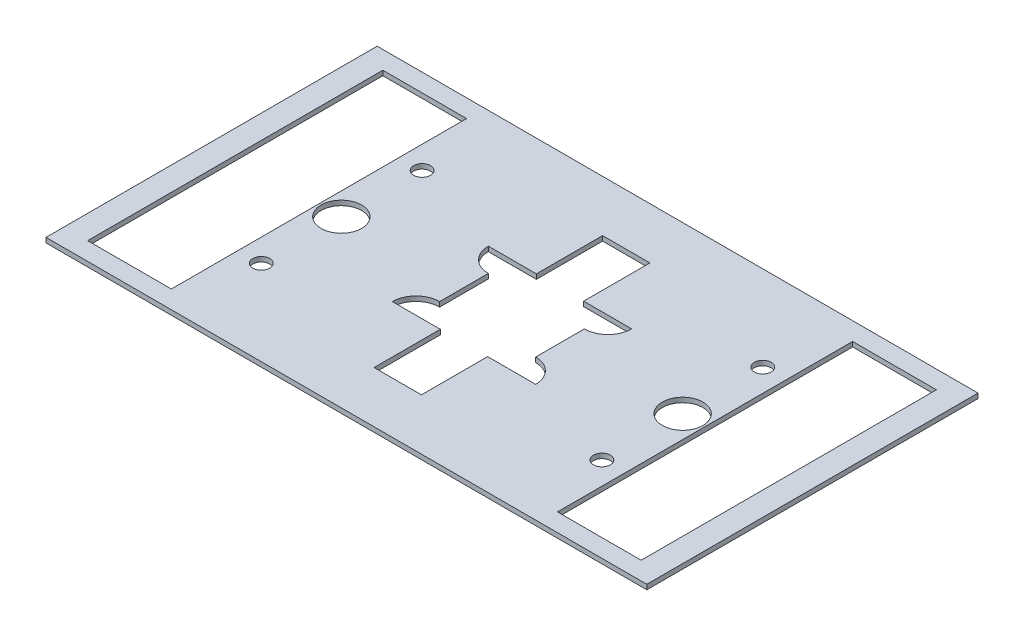
SolidWorks part; units mm, degrees
material "Copper"
ref_plane "Front Plane" through (0, 0, 0) normal (0, 0, 1) x (1, 0, 0)
ref_plane "Top Plane" through (0, 0, 0) normal (0, 1, 0) x (1, 0, 0)
ref_plane "Right Plane" through (0, 0, 0) normal (1, 0, 0) x (0, 0, -1)
sketch "Sketch1" plane through (0, 0, 0) normal (0, 1, 0) x (1, 0, 0)
  line L0 (-2.5, 5.075) -> (-2.5, 12.075)
  line L1 (-5, 5) -> (5, 5) construction
  line L2 (-5, 5) -> (-5, -5) construction
  line L3 (-5, -5) -> (5, -5) construction
  line L4 (5, 5) -> (5, -5) construction
  line L5 (-5.075, 5.075) -> (5.075, 5.075)
  line L6 (-5.075, 5.075) -> (-5.075, -5.075)
  line L7 (-5.075, -5.075) -> (5.075, -5.075)
  line L8 (5.075, 5.075) -> (5.075, -5.075)
  line L9 (-7.575, 7.575) -> (7.575, 7.575)
  line L10 (-7.575, 7.575) -> (-7.575, -7.575)
  line L11 (-7.575, -7.575) -> (7.575, -7.575)
  line L12 (7.575, 7.575) -> (7.575, -7.575)
  line L13 (-31.75, 17.75) -> (31.75, 17.75) construction
  line L14 (-31.75, 17.75) -> (-31.75, -17.75) construction
  line L15 (-31.75, -17.75) -> (31.75, -17.75) construction
  line L16 (31.75, 17.75) -> (31.75, -17.75) construction
  line L17 (-31.75, 17.5) -> (31.75, 17.5)
  line L18 (-31.75, 17.5) -> (-31.75, -17.5)
  line L19 (-31.75, -17.5) -> (31.75, -17.5)
  line L20 (31.75, 17.5) -> (31.75, -17.5)
  line L21 (-29.25, 15.6) -> (-20.4, 15.6)
  line L22 (-29.25, 15.6) -> (-29.25, -15.6)
  line L23 (-29.25, -15.6) -> (-20.4, -15.6)
  line L24 (-20.4, 15.6) -> (-20.4, -15.6)
  line L25 (20.4, 15.6) -> (29.25, 15.6)
  line L26 (20.4, 15.6) -> (20.4, -15.6)
  line L27 (20.4, -15.6) -> (29.25, -15.6)
  line L28 (29.25, 15.6) -> (29.25, -15.6)
  line L29 (-2.5, 12.075) -> (2.5, 12.075)
  line L30 (2.5, 12.075) -> (2.5, 5.075)
  line L31 (-2.5, -5.075) -> (-2.5, -12.075)
  line L32 (-2.5, -12.075) -> (2.5, -12.075)
  line L33 (2.5, -12.075) -> (2.5, -5.075)
  line L34 (-5.075, 5.075) -> (-5.075, 7.575)
  line L35 (5.075, 5.075) -> (5.075, 7.575)
  line L36 (5.075, -5.075) -> (5.075, -7.575)
  line L37 (-5.075, -5.075) -> (-5.075, -7.575)
  line L38 (-5.075, 5.075) -> (-7.575, 5.075)
  line L39 (5.075, 5.075) -> (7.575, 5.075)
  line L40 (-5.075, -5.075) -> (-7.575, -5.075)
  line L41 (5.075, -5.075) -> (7.575, -5.075)
  circle A0 centre (-5.075, 5.075) radius 2.5
  circle A1 centre (5.075, 5.075) radius 2.5
  circle A2 centre (5.075, -5.075) radius 2.5
  circle A3 centre (-5.075, -5.075) radius 2.5
  circle A4 centre (-18, 8.5) radius 0.889
  circle A5 centre (18, 8.5) radius 0.889
  circle A6 centre (18, -8.5) radius 0.889
  circle A7 centre (-18, -8.5) radius 0.889
  circle A8 centre (-18.034, 0) radius 2.1446
  circle A9 centre (18.034, 0) radius 2.1446
  point P4 (0, 5.075)
  point P13 (5.075, 0)
  point P14 (0, 5)
  point P16 (5, 0)
  point P25 (0, 17.75)
  point P26 (0, 7.575)
  point P31 (7.575, 0)
  point P32 (31.75, 0)
  point P37 (0, 17.5)
  point P38 (31.75, 0)
  point P47 (-29.25, 0)
  point P48 (-31.75, 0)
  point P63 (0, 12.075)
  point P72 (0, -12.075)
  dimension "D3" = 5
  dimension "D18" = 1.778
  dimension "D21" = 4.2892
  dimension "D1" = 10
  dimension "D2" = 10.15
  dimension "D4" = 35.5
  dimension "D5" = 63.5
  dimension "D6" = 63.5
  dimension "D7" = 35
  dimension "D8" = 2.15
  dimension "D10" = 31.2
  dimension "D11" = 8.85
  dimension "D12" = 2.15
  dimension "D14" = 18
  dimension "D15" = 8.5
  dimension "D16" = 8.5
  dimension "D17" = 18
  dimension "D19" = 18.034
  dimension "D20" = 18.034
  dimension "D22" = 5
  dimension "D23" = 7
  dimension "D24" = 7
  dimension "D13" = 2.5
  dimension "D9" = 2.5
extrude "Boss-Extrude1" add sketch "Sketch1" along normal blind 0.508 contours L20 L17 L18 L19 A9 A8 A7 A6 A5 A4 L9 L12 L11 L10 L21 L24 L23 L22 L25 L28 L27 L26 | A2 L11 L12 | A2 L12 A1 L8 | A1 L12 L9 | A0 L9 L10 | A3 L6 A0 L10 | A3 L10 L11 | A0 L5 L0 L9 | A1 L9 L30 L5 | A2 L7 L33 L11 | A3 L11 L31 L7 | L5 A0 L34 | L35 A1 L5 | L7 A2 L36 | L37 A3 L7 | L34 A0 L38 | L39 A1 L35 | L36 A2 L8 | L40 A3 L37 region at (-3.0603, 0, -6.9318) region at (-4.014, 0, -6.136) region at (3.0603, 0, -6.9318) region at (-7.0166, 0, -7.0166) region at (-6.136, 0, -6.136) region at (-6.4442, 0, 0) region at (4.014, 0, -6.136) region at (6.136, 0, -6.136) region at (7.0166, 0, -7.0166) region at (6.4442, 0, 0) region at (-7.0166, 0, 7.0166) region at (-6.136, 0, 6.136) region at (-4.014, 0, 6.136) region at (-3.0603, 0, 6.9318) region at (6.136, 0, 6.136) region at (7.0166, 0, 7.0166) region at (4.014, 0, 6.136) region at (3.0603, 0, 6.9318) region at (0, 0, -16.7749)
equation "\"D2@Sketch1\"=\"D1@Sketch1\"+0.15"
equation "\"D17@Sketch1\"=\"D14@Sketch1\""
equation "\"D18@Sketch1\"=0.0700in"
equation "\"D20@Sketch1\"=\"D19@Sketch1\""
equation "\"D24@Sketch1\"=\"D23@Sketch1\""
equation "\"D9@Sketch1\"=\"D13@Sketch1\""
